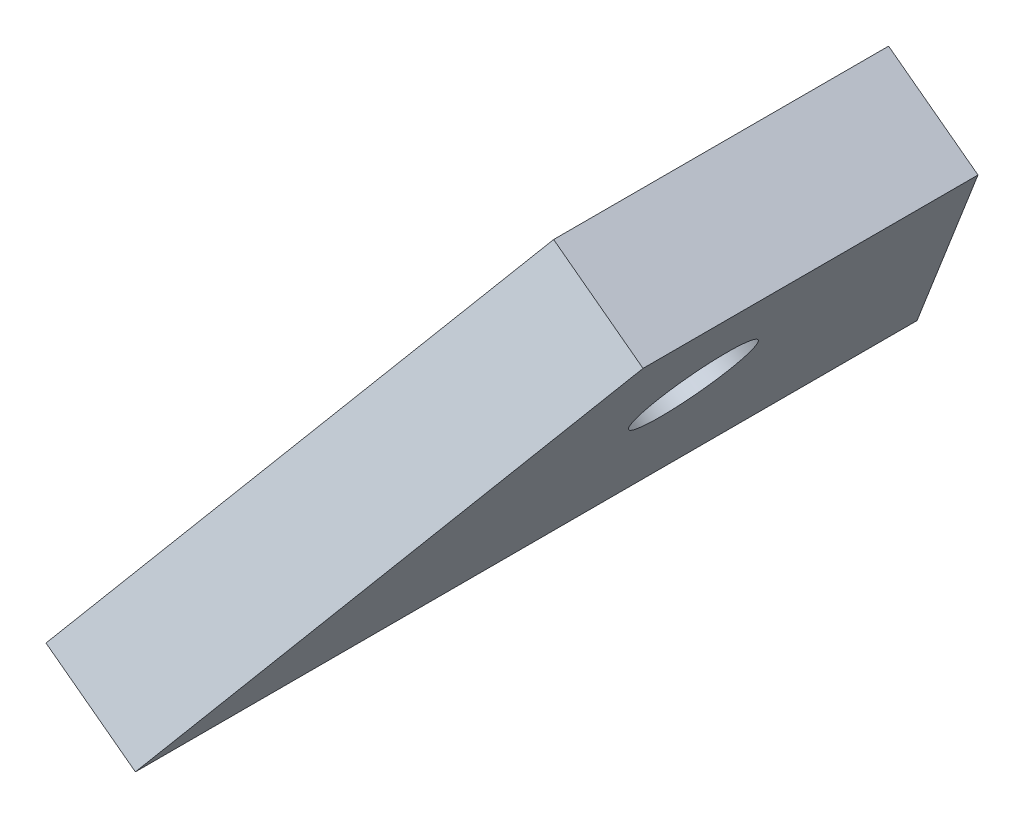
SolidWorks part; units mm, degrees
ref_plane "Alzado" through (0, 0, 0) normal (0, 0, 1) x (1, 0, 0)
ref_plane "Planta" through (0, 0, 0) normal (0, 1, 0) x (1, 0, 0)
ref_plane "Vista lateral" through (0, 0, 0) normal (1, 0, 0) x (0, 0, -1)
sketch3d "Sk_Plano_Yugo"
  point P0 (-234.5664, 351.3361, 0)
  point P1 (-234.5664, 351.3361, 10)
  point P2 (-228.5751, 359.3426, 0)
ref_plane "Plano_Yugo" through (-318.9017, 238.633, 0) normal (-0.8007, 0.5991, 0) x (0, 0, 1)
sketch "Sk_Yugo" plane through (-318.9017, 238.633, 0) normal (-0.8007, 0.5991, 0) x (0, 0, 1)
  line L0 (-14, 203.7638) -> (14, 203.7638)
  line L1 (14, 203.7638) -> (6, 220.7638)
  line L2 (6, 220.7638) -> (-6, 220.7638)
  line L3 (-6, 220.7638) -> (-14, 203.7638)
extrude "Yugo" add sketch "Sk_Yugo" along normal blind 4
sketch3d "Sk_Ojo_cable"
  line L0 (-190.0295, 409.1847, 0) -> (-194.8334, 412.7795, 0)
  dimension "D1" = 6
sweep "Ojo_cable" cut path "Sk_Ojo_cable" circular profile diameter 4 parameters "D3"=4
